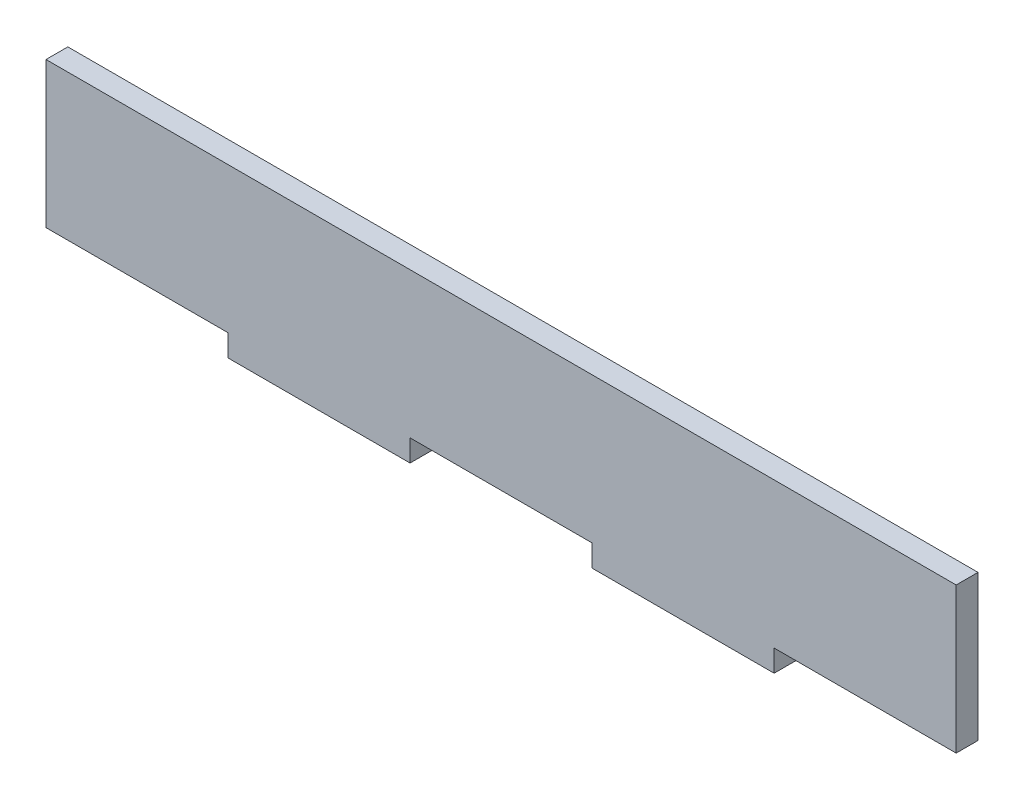
SolidWorks part; units mm, degrees
material "Pine"
ref_plane "Front Plane" through (0, 0, 0) normal (0, 0, 1) x (1, 0, 0)
ref_plane "Top Plane" through (0, 0, 0) normal (0, 1, 0) x (1, 0, 0)
ref_plane "Right Plane" through (0, 0, 0) normal (1, 0, 0) x (0, 0, -1)
sketch "Sketch1" plane through (0, 0, 0) normal (0, 0, 1) x (1, 0, 0)
  line L1 (-125, 23) -> (125, 23)
  line L2 (-125, 23) -> (-125, -23)
  line L3 (-125, -23) -> (125, -23)
  line L4 (125, 23) -> (125, -23)
  line L5 (-125, 23) -> (125, -23) construction
  line L6 (-125, -23) -> (125, 23) construction
  point P0 (0, 0)
  dimension "D1" = 46
  dimension "D2" = 250
extrude "Boss-Extrude1" add sketch "Sketch1" along normal blind 6
sketch "Sketch2" plane through (0, 0, 6) normal (0, 0, 1) x (1, 0, 0)
  line L0 (-25, -23) -> (-25, -17)
  line L1 (-125, -23) -> (-75, -23)
  line L2 (-125, -23) -> (-125, -17)
  line L3 (-125, -17) -> (-75, -17)
  line L4 (-75, -23) -> (-75, -17)
  line L5 (-25, -23) -> (25, -23)
  line L6 (25, -23) -> (25, -17)
  line L7 (-25, -17) -> (25, -17)
  line L8 (75, -23) -> (75, -17)
  line L9 (75, -23) -> (125, -23)
  line L10 (125, -23) -> (125, -17)
  line L11 (75, -17) -> (125, -17)
  dimension "D1" = 50
  dimension "D2" = 6
  dimension "D3" = 3
extrude "Cut-Extrude1" cut sketch "Sketch2" against normal blind 6
